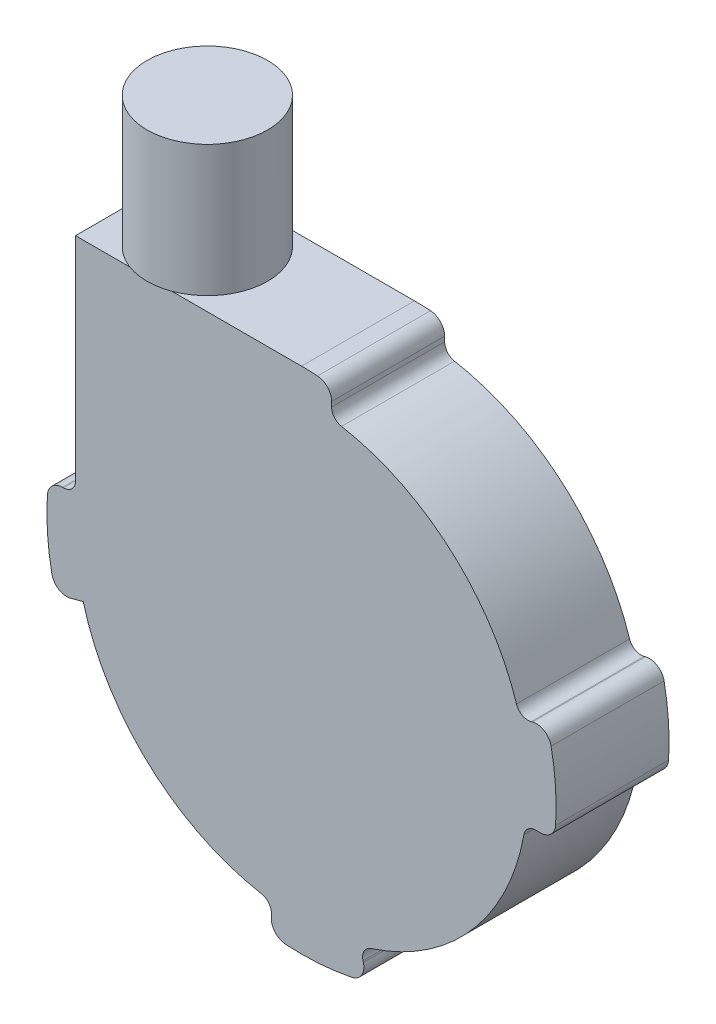
SolidWorks part; units mm, degrees
ref_plane "Front Plane" through (0, 0, 0) normal (0, 0, 1) x (1, 0, 0)
ref_plane "Top Plane" through (0, 0, 0) normal (0, 1, 0) x (1, 0, 0)
ref_plane "Right Plane" through (0, 0, 0) normal (1, 0, 0) x (0, 0, -1)
sketch "Sketch1" plane through (0, 0, 0) normal (0, 0, 1) x (1, 0, 0)
  line L0 (0, 42.926) -> (-38.1, 42.926)
  line L1 (-38.1, 42.926) -> (-38.1, 7.112)
  line L2 (-5.08, -39.4968) -> (-5.08, -40.306)
  line L3 (10.432, -38.9327) -> (10.3736, -38.7148)
  line L4 (0, 0) -> (0, -42.926) construction
  line L5 (-38.9327, -10.432) -> (-36.8018, -9.861)
  line L6 (-40.132, 5.08) -> (-40.306, 5.08)
  line L7 (-10.432, 38.9327) -> (-9.861, 36.8018) construction
  line L8 (5.08, 39.4968) -> (5.08, 40.306)
  line L9 (38.9327, 10.432) -> (38.7148, 10.3736)
  line L10 (39.4968, -5.08) -> (40.306, -5.08)
  circle A0 centre (0, 0) radius 42.926 construction
  circle A1 centre (0, 0) radius 38.1 construction
  arc A2 (-2.6997, -42.841) -> (8.4803, -42.08) centre (0, 0) ccw
  arc A3 (-2.6997, -42.841) -> (-5.08, -40.306) centre (-2.54, -40.306) cw
  arc A4 (10.432, -38.9327) -> (8.4803, -42.08) centre (7.9785, -39.5901) cw
  arc A5 (-38.9327, -10.432) -> (-42.08, -8.4803) centre (-39.5901, -7.9785) cw
  arc A6 (-42.841, 2.6997) -> (-42.08, -8.4803) centre (0, 0) ccw
  arc A7 (-42.841, 2.6997) -> (-40.306, 5.08) centre (-40.306, 2.54) cw
  arc A8 (-10.432, 38.9327) -> (-8.4803, 42.08) centre (-7.9785, 39.5901) cw construction
  arc A9 (2.6997, 42.841) -> (-8.4803, 42.08) centre (0, 0) ccw construction
  arc A10 (2.6997, 42.841) -> (5.08, 40.306) centre (2.54, 40.306) cw
  arc A11 (38.9327, 10.432) -> (42.08, 8.4803) centre (39.5901, 7.9785) cw
  arc A12 (42.841, -2.6997) -> (42.08, 8.4803) centre (0, 0) ccw
  arc A13 (42.841, -2.6997) -> (40.306, -5.08) centre (40.306, -2.54) cw
  arc A14 (-36.8018, -9.861) -> (-6.7519, -37.497) centre (0, 0) ccw
  arc A15 (37.497, -6.7519) -> (11.7117, -36.2553) centre (0, 0) cw
  arc A16 (6.7519, 37.497) -> (36.2553, 11.7117) centre (0, 0) cw
  arc A17 (-38.1, 7.112) -> (-40.132, 5.08) centre (-40.132, 7.112) cw
  arc A18 (6.7519, 37.497) -> (5.08, 39.4968) centre (7.112, 39.4968) cw
  arc A19 (36.2553, 11.7117) -> (38.7148, 10.3736) centre (38.1889, 12.3364) ccw
  arc A20 (37.497, -6.7519) -> (39.4968, -5.08) centre (39.4968, -7.112) cw
  arc A21 (11.7117, -36.2553) -> (10.3736, -38.7148) centre (12.3364, -38.1889) ccw
  arc A22 (-6.7519, -37.497) -> (-5.08, -39.4968) centre (-7.112, -39.4968) cw
  arc A23 (0, 42.926) -> (2.6997, 42.841) centre (0, 0) cw
  point P15 (-5.08, -42.6243)
  point P18 (11.1101, -41.4633)
  point P46 (0, 0)
  point P56 (9.861, -36.8018)
  point P59 (-5.08, -37.7598)
  dimension "D1" = 85.852
  dimension "D2" = 76.2
  dimension "D5" = 2.54
  dimension "D7" = 2.032
  dimension "D3" = 15
  dimension "D4" = 5.08
  dimension "D6" = 4
extrude "Boss-Extrude1" add sketch "Sketch1" against normal blind 19.05
sketch "Sketch3" plane through (0, 42.926, 0) normal (0, 1, 0) x (1, 0, 0)
  line L1 (-25.4, 19.05) -> (-25.4, 0) construction
  line L2 (0, 19.05) -> (-38.1, 19.05) construction
  line L3 (0, 0) -> (-38.1, 0) construction
  line L4 (0, 19.05) -> (0, 0) construction
  circle A0 centre (-25.4, 9.525) radius 10.16
  dimension "D2" = 20.32
  dimension "D1" = 25.4
extrude "Boss-Extrude2" add sketch "Sketch3" along normal blind 22.098
ref_plane "Plane1" through (0, 0, -9.525) normal (0, 0, 1) x (1, 0, 0)
